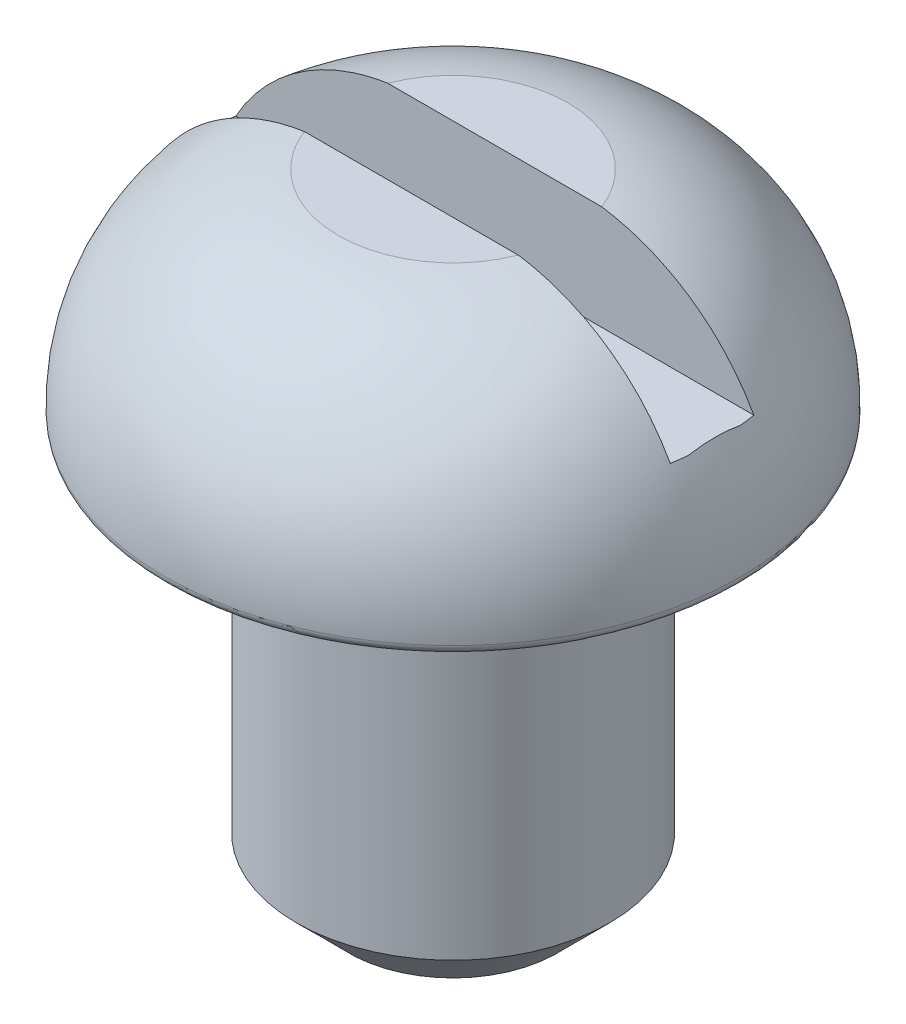
SolidWorks part; units mm, degrees
ref_plane "Спереди" through (0, 0, 0) normal (0, 0, 1) x (1, 0, 0)
ref_plane "Сверху" through (0, 0, 0) normal (0, 1, 0) x (1, 0, 0)
ref_plane "Справа" through (0, 0, 0) normal (1, 0, 0) x (0, 0, -1)
sketch "Эскиз1" plane through (0, 0, 0) normal (0, 0, 1) x (1, 0, 0)
  line L0 (2.75, 3.9) -> (1.5, 3.9)
  line L1 (0, 0) -> (0, 6)
  line L2 (1.5, 3.9) -> (1.5, 0.5)
  line L3 (1.5, 0.5) -> (1, 0)
  line L4 (1, 0) -> (0, 0)
  line L5 (0, 6) -> (1.1, 6)
  arc A0 (1.1, 6) -> (2.75, 3.9) centre (0.7797, 4.0501) cw
  dimension "D2" = 1.1
  dimension "D8" = 2.1
  dimension "D1" = 6
  dimension "D3" = 1.5
  dimension "D4" = 1
  dimension "D5" = 2.1
  dimension "D6" = 2.75
  dimension "D7" = 45
  dimension "D9" = 1.5
revolve "Повернуть1" add sketch "Эскиз1" angle 360 about L1
fillet "Скругление1" radius 0.1 1 edges at (0, 3.9, -2.75)
sketch "Эскиз3" plane through (0, 6, 0) normal (0, 1, 0) x (-1, 0, 0)
  line L1 (2.5, -0.4) -> (-2.5, -0.4)
  line L2 (2.5, -0.4) -> (2.5, 0.4)
  line L3 (2.5, 0.4) -> (-2.5, 0.4)
  line L4 (-2.5, -0.4) -> (-2.5, 0.4)
  dimension "D1" = 0.8
  dimension "D2" = 0.4
  dimension "D3" = 5
  dimension "D4" = 2.5
extrude "Вырез-Вытянуть2" cut sketch "Эскиз3" against normal blind 1
ref_axis "Ось1" through (0, -104.1565, 0) along (0, 1, 0)
